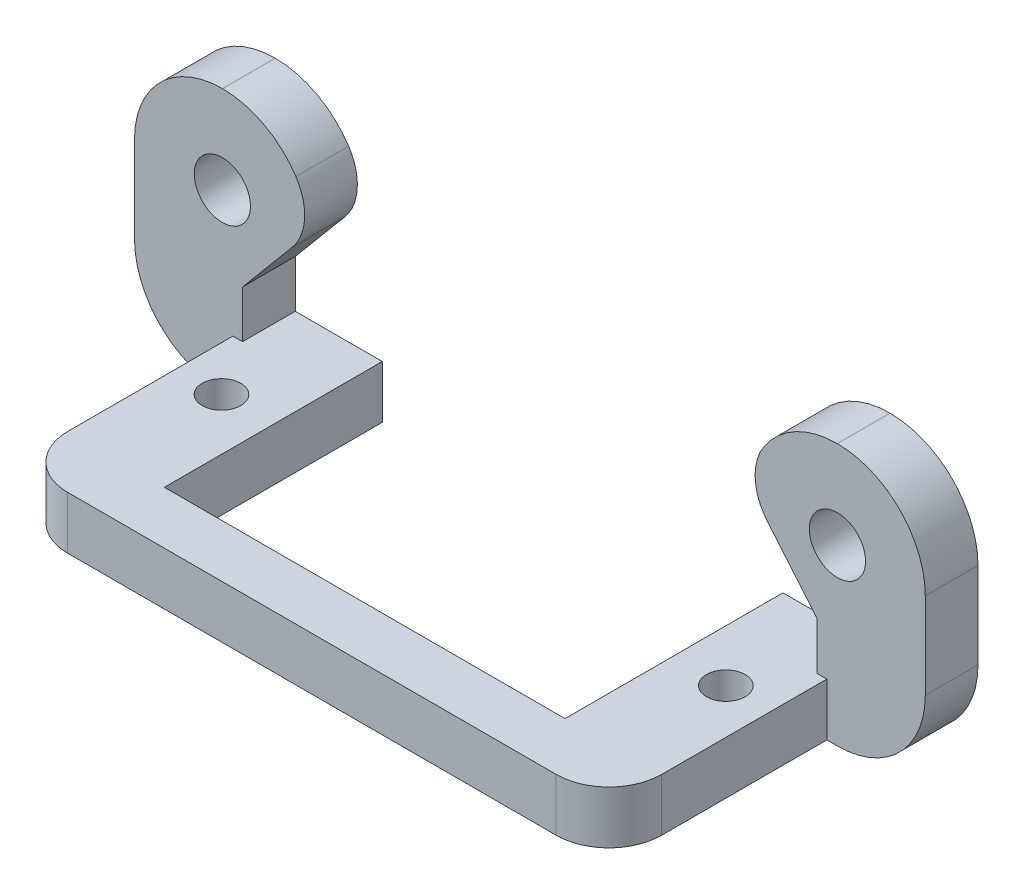
SolidWorks part; units mm, degrees
ref_plane "Front Plane" through (0, 0, 0) normal (0, 0, 1) x (1, 0, 0)
ref_plane "Top Plane" through (0, 0, 0) normal (0, 1, 0) x (1, 0, 0)
ref_plane "Right Plane" through (0, 0, 0) normal (1, 0, 0) x (0, 0, -1)
sketch "Sketch1" plane through (0, 0, 0) normal (0, 1, 0) x (1, 0, 0)
  line L0 (16.9, -11.7) -> (16.9, 11.7)
  line L1 (11.4, -6.2) -> (-11.4, -6.2)
  line L2 (11.4, -6.2) -> (11.4, 6.2)
  line L3 (11.4, 6.2) -> (-11.4, 6.2)
  line L4 (-11.4, -6.2) -> (-11.4, 6.2)
  line L5 (11.4, -6.2) -> (-11.4, 6.2) construction
  line L6 (11.4, 6.2) -> (-11.4, -6.2) construction
  line L7 (16.9, 11.7) -> (-16.9, 11.7)
  line L8 (-16.9, -11.7) -> (-16.9, 11.7)
  line L9 (16.9, -11.7) -> (-16.9, -11.7)
  line L10 (-11.4, 6.2) -> (-16.9, 6.2)
  line L11 (11.4, 6.2) -> (16.9, 6.2)
  line L12 (-16.9, -9.2) -> (16.9, -9.2)
  line L13 (0, 11.7) -> (0, -11.7) construction
  circle A0 centre (-14.35, 0) radius 1.1
  circle A1 centre (14.35, 0) radius 1.1
  point P0 (0, 0)
  dimension "D5" = 2.2
  dimension "D6" = 2.95
  dimension "D1" = 5.5
  dimension "D2" = 22.8
  dimension "D3" = 12.4
  dimension "D4" = 3
  dimension "D7" = 6.2
extrude "Boss-Extrude1" add sketch "Sketch1" along normal blind 3 contours L11 L2 L1 L4 L10 L8 L9 L0
fillet "Fillet1" radius 3 2 edges at (16.9, 1.5, 9.2) (-16.9, 1.5, 9.2)
sketch "Sketch2" plane through (0, 0, -6.2) normal (0, 0, -1) x (-1, 0, 0)
  line L0 (-11.4, 3) -> (11.4, 3) construction
  line L1 (-16.35, 3) -> (-16.35, 5.7)
  line L2 (-16.35, 5.7) -> (-12.5, 10.2883)
  line L3 (-12.5, 10.2883) -> (-12.5, 14.9)
  line L4 (-22.5, 4.9) -> (22.5, 4.9) construction
  line L5 (-22.5, 4.9) -> (-22.5, 14.9) construction
  line L6 (-22.5, 14.9) -> (22.5, 14.9) construction
  line L8 (-22.5, 14.9) -> (-12.5, 4.9) construction
  line L9 (-22.5, 14.9) -> (-12.5, 14.9)
  line L10 (-22.5, 14.9) -> (-22.5, 4.9)
  line L11 (-22.5, 4.9) -> (-16.35, 4.9) construction
  line L12 (-12.5, 14.9) -> (-12.5, 4.9) construction
  line L13 (-12.5, 14.9) -> (-22.5, 4.9) construction
  line L14 (0, 14.9) -> (0, 0) construction
  line L15 (-22.5, 4.9) -> (-22.5, 0)
  line L16 (-22.5, 0) -> (-16.9, 0)
  line L17 (-16.9, 0) -> (-16.9, 3)
  line L18 (-16.35, 3) -> (-16.35, 4.9) construction
  line L19 (-11.4, 3) -> (-16.9, 3) construction
  line L20 (-12.5, 3) -> (-12.5, 4.9) construction
  line L21 (22.5, 14.9) -> (22.5, 4.9)
  line L22 (22.5, 14.9) -> (12.5, 14.9)
  line L23 (12.5, 10.2883) -> (12.5, 14.9)
  line L24 (16.35, 5.7) -> (12.5, 10.2883)
  line L25 (16.35, 3) -> (16.35, 5.7)
  line L30 (-13.25, 3) -> (-15.45, 3) construction
  line L31 (-13.25, 3) -> (-15.45, 3) construction
  line L32 (-16.9, 3) -> (-16.35, 3)
  line L33 (16.9, 3) -> (16.35, 3)
  line L34 (16.9, 0) -> (16.9, 3)
  line L35 (22.5, 0) -> (16.9, 0)
  line L36 (22.5, 4.9) -> (22.5, 0)
  circle A0 centre (-17.5, 9.9) radius 1.6
  circle A2 centre (17.5, 9.9) radius 1.6
  point P3 (0, 4.9)
  point P36 (-14.35, 3)
  dimension "D5" = 3.2
  dimension "D1" = 1.9
  dimension "D2" = 10
  dimension "D3" = 45
  dimension "D4" = 10
  dimension "D6" = 2
  dimension "D7" = 2.7
  dimension "D8" = 140
extrude "Boss-Extrude2" add sketch "Sketch2" against normal blind 3
fillet "Fillet2" radius 5 6 edges at (22.5, 0, -4.7) (-22.5, 0, -4.7) (-22.5, 14.9, -4.7) (-12.5, 14.9, -4.7) (12.5, 14.9, -4.7) (22.5, 14.9, -4.7)
fillet "Fillet3" radius 3 2 edges at (12.5, 10.2883, -4.7) (-12.5, 10.2883, -4.7)
